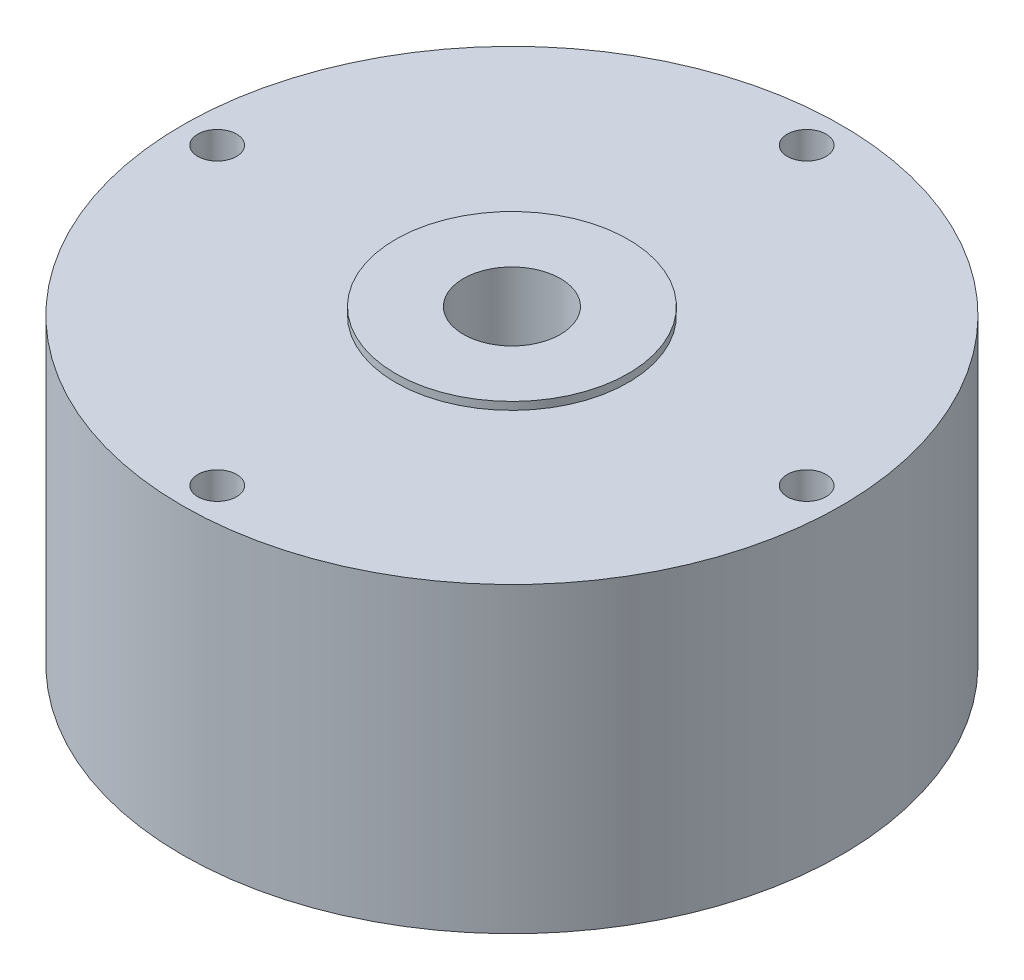
SolidWorks part; units mm, degrees
ref_plane "Front plane" through (0, 0, 0) normal (0, 0, 1) x (1, 0, 0)
ref_plane "Top plane" through (0, 0, 0) normal (0, 1, 0) x (1, 0, 0)
ref_plane "Right plane" through (0, 0, 0) normal (1, 0, 0) x (0, 0, -1)
ref_axis "Axis X" through (0, 0, 0) along (1, 0, 0)
ref_axis "Axis Y" through (0, 0, 0) along (0, 1, 0)
ref_axis "Axis Z" through (0, 0, 0) along (0, 0, 1)
sketch "Sketch1" plane through (0, 0, 0) normal (0, 1, 0) x (1, 0, 0)
  circle A0 centre (0, 0) radius 17
  dimension "D1" = 34
extrude "Extrude1" add sketch "Sketch1" along normal blind 16
sketch "Sketch2" plane through (0, 16, 0) normal (0, 1, 0) x (1, 0, 0)
  circle A0 centre (0, 0) radius 6
  circle A1 centre (0, 0) radius 17
  dimension "D1" = 34
  dimension "D2" = 12
extrude "Extrude2" cut sketch "Sketch2" against normal blind 0.4
sketch "Sketch3" plane through (0, 16, 0) normal (0, 1, 0) x (1, 0, 0)
  line L0 (0, 0) -> (0, 15.2028) construction
  circle A0 centre (0, 0) radius 15.2028 construction
  circle A1 centre (0, 15.2028) radius 1
  circle A2 centre (15.2028, 0) radius 1
  circle A3 centre (0, -15.2028) radius 1
  circle A4 centre (-15.2028, 0) radius 1
  dimension "D1" = 30.4056
  dimension "D2" = 2
extrude "Extrude3" cut sketch "Sketch3" against normal blind 3.4
sketch "Sketch4" plane through (0, 0, 0) normal (0, -1, 0) x (1, 0, 0)
  line L0 (0, 0) -> (0, 5) construction
  circle A0 centre (0, 0) radius 5 construction
  circle A1 centre (0, 5) radius 1.25
  circle A2 centre (5, 0) radius 1.25
  circle A3 centre (0, -5) radius 1.25
  circle A4 centre (-5, 0) radius 1.25
  dimension "D1" = 2.5
  dimension "D3" = 10
  dimension "D2" = 4
extrude "Extrude4" [suppressed] cut sketch "Sketch4" against normal blind 3
sketch "Sketch5" plane through (0, 0, 0) normal (0, -1, 0) x (1, 0, 0)
  line L1 (-11, 6) -> (11, 6) construction
  line L2 (-11, 6) -> (-11, -6) construction
  line L3 (-11, -6) -> (11, -6) construction
  line L4 (11, 6) -> (11, -6) construction
  line L5 (-11, 6) -> (11, -6) construction
  line L6 (-11, -6) -> (11, 6) construction
  circle A0 centre (-11, 6) radius 1.25
  circle A1 centre (11, 6) radius 1.25
  circle A2 centre (11, -6) radius 1.25
  circle A3 centre (-11, -6) radius 1.25
  point P0 (0, 0)
  dimension "D1" = 2.5
  dimension "D2" = 2.5
  dimension "D3" = 2.5
  dimension "D4" = 2.5
  dimension "D5" = 22
  dimension "D6" = 12
extrude "Extrude5" cut sketch "Sketch5" against normal blind 3
chamfer "Chamfer1" [suppressed] distance 0.5 angle 45
sketch "Sketch6" plane through (0, 0, 0) normal (0, -1, 0) x (1, 0, 0)
  circle A0 centre (0, 0) radius 2.5
  dimension "D1" = 5
extrude "Extrude6" cut sketch "Sketch6" against normal through all
equation "\"motor_D\"= 34'Motor diameter"
equation "\"motor_H\"= 16'Motor heigh"
equation "\"motor_d1\"= 30.4056'Seating diameter of screws on the fixed part of the motor"
equation "\"motor_s1\"= 2'Screws diameter on the fixed part of motor"
equation "\"motor_d2\"= 0'Seating diameter of screws on the moving part of the motor (if this parameter is not determine, write 0)"
equation "\"motor_s2\"= 2.5'Screws diameter on the moving part of motor"
equation "\"motor_Dc\"= 5'Central hole diameter of motor"
equation "\"bearing_d1\"= 8'Bearing inner diameter"
equation "\"bearing_d2\"= 16'Bearing external diameter"
equation "\"bearing h\"= 5'Bearing heigh"
equation "\"pin_d\"= 2'Pin diameter"
equation "\"pin_h\"= 12'Pin heigh"
equation "\"magnet_d1\"= 5'Magnet inner diameter"
equation "\"magnet_d2\"= 9.5'Magnet external diameter"
equation "\"magnet_h\"= 3'Magnet heigh"
equation "\"motor_a2\"= 12'Seating parameter in rectangle of screws on the moving part of the motor"
equation "\"motor_b2\"= 22'Seating parameter in rectangle of screws on the moving part of the motor"
equation "\"D1@Sketch1\"=\"motor_D\""
equation "\"D1@Extrude1\"=\"motor_H\""
equation "\"D1@Sketch2\"=\"motor_D\""
equation "\"motor_cmd\"= 12'Central magnet mount diameter"
equation "\"motor_cmh\"= 0.4'Central magnet mount heigh (if not write 0)"
equation "\"D2@Sketch2\"=\"motor_cmd\""
equation "\"D1@Extrude2\"= \"motor_cmh\""
equation "\"Extrude2\"= IIF ( \"motor_cmh\" = 0 , \"suppressed\" , \"unsuppressed\" )"
equation "\"D1@Sketch3\"=\"motor_d1\""
equation "\"D2@Sketch3\"=\"motor_s1\""
equation "\"D1@Extrude3\"=\"motor_cmh\"+3"
equation "\"D1@Sketch4\"=\"motor_s2\""
equation "\"D3@Sketch4\"=if( \"motor_d2\"=0,10,\"motor_d2\")"
equation "\"Extrude4\"= IIF ( \"motor_d2\" = 0 , \"suppressed\" , \"unsuppressed\" )"
equation "\"D1@Sketch5\"=\"motor_s2\""
equation "\"D2@Sketch5\"=\"D1@Sketch5\""
equation "\"D3@Sketch5\"=\"D2@Sketch5\""
equation "\"D4@Sketch5\"=\"D2@Sketch5\""
equation "\"D5@Sketch5\"=\"motor_b2\""
equation "\"D6@Sketch5\"=\"motor_a2\""
equation "\"Extrude5\"= IIF ( \"motor_d2\" = 0 , \"unsuppressed\" , \"suppressed\" )"
equation "\"D1@Sketch6\"=\"motor_Dc\""
equation "\"motor_whR\"= 10'Distance from center of motor to wires"
equation "\"print_offset\"= 0.2'Offset for printing holes"
equation "\"ft_sensor_d1\"= 9.8"
equation "\"ft_sensor_d2\"= 24.9"
equation "\"ft_sensor_d3\"= 22.6'Inner diameter of "
equation "\"ft_sensor_h\"= 7.1"
equation "\"ft_sensor_whD\" = 5"
